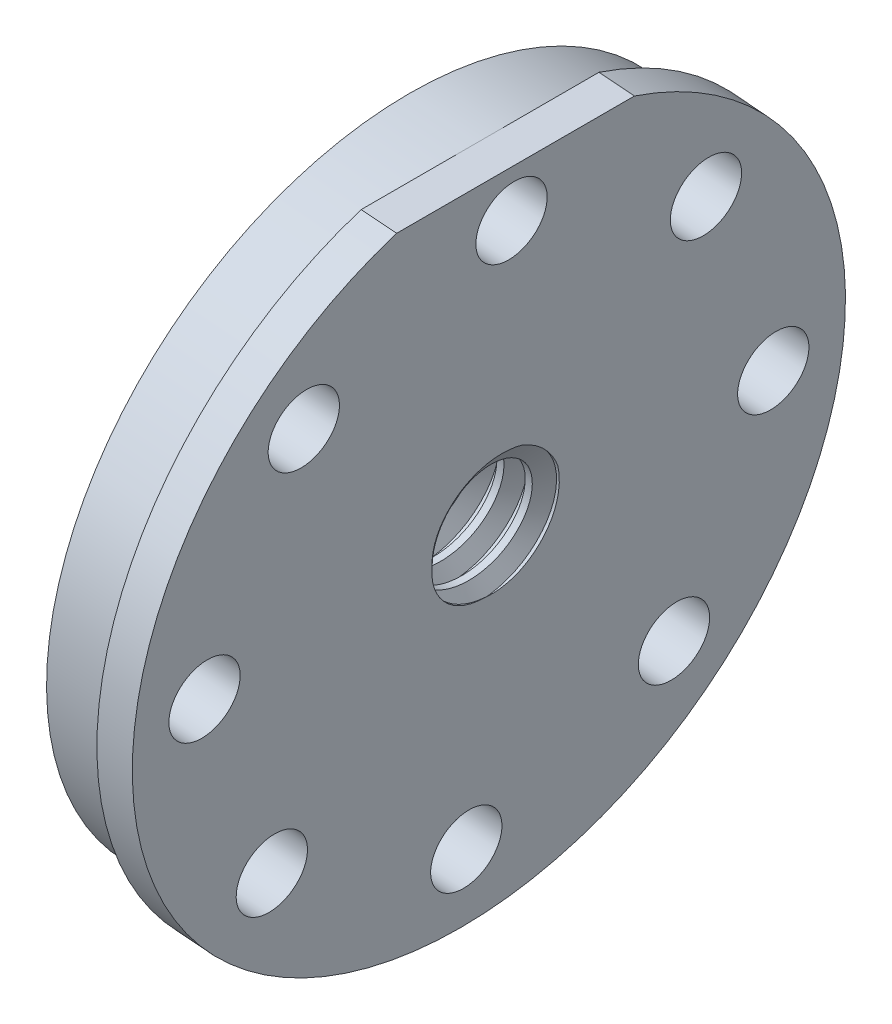
SolidWorks part; units mm, degrees
ref_plane "Front Plane" through (0, 0, 0) normal (0, 0, 1) x (1, 0, 0)
ref_plane "Top Plane" through (0, 0, 0) normal (0, 1, 0) x (1, 0, 0)
ref_plane "Right Plane" through (0, 0, 0) normal (1, 0, 0) x (0, 0, -1)
sketch "Sketch1" plane through (234.2789, -18.689, 0) normal (0.9968, -0.0795, 0) x (0, 0, -1)
  circle A1 centre (-43.1743, 8.5503) radius 14.9606
  dimension "D1" = 29.9212
extrude "Boss-Extrude1" add sketch "Sketch1" against normal blind 4.7625
sketch "Sketch2" plane through (234.2789, -18.689, 0) normal (0.9968, -0.0795, 0) x (0, 0, -1)
  circle A0 centre (-43.1743, 8.5503) radius 2.54
  dimension "D1" = 5.08
extrude "Cut-Extrude1" cut sketch "Sketch2" against normal blind 6.35
sketch "Sketch3" plane through (229.5315, -18.3103, 0) normal (-0.9968, 0.0795, 0) x (0, 0, 1)
  circle A0 centre (43.1743, 21.2503) radius 1.5875
  circle A1 centre (43.1743, 8.5503) radius 14.9606 construction
  circle A2 centre (43.1743, 8.5503) radius 14.9606
  circle A3 centre (52.1545, 17.5306) radius 1.5875
  circle A4 centre (55.8743, 8.5503) radius 1.5875
  circle A5 centre (52.1545, -0.4299) radius 1.5875
  circle A6 centre (43.1743, -4.1497) radius 1.5875
  circle A7 centre (34.194, -0.4299) radius 1.5875
  circle A8 centre (30.4743, 8.5503) radius 1.5875
  circle A9 centre (34.194, 17.5306) radius 1.5875
  point P21 (43.1743, 8.5503)
  dimension "D1" = 3.175
  dimension "D3" = 12.7
  dimension "D2" = 8
extrude "Cut-Extrude2" cut sketch "Sketch3" against normal blind 10 contours A8 | A0 | A3 | A4 | A5 | A6 | A7 | A9 region at (231.2213, 2.8727, 43.1743) region at (230.9255, -0.8352, 52.1545) region at (230.2114, -9.787, 55.8743) region at (229.4973, -18.7389, 52.1545) region at (229.2015, -22.4468, 43.1743) region at (229.4973, -18.7389, 34.194) region at (230.2114, -9.787, 30.4743)
sketch "Sketch4" plane through (234.2789, -18.689, 0) normal (0.9968, -0.0795, 0) x (0, 0, -1)
  line L0 (-58.1349, 8.5503) -> (-28.2137, 8.5503) construction
  circle A0 centre (-43.1743, 8.5503) radius 14.9606 construction
thread "Thread1" pitch 1.27 method cut profile "Thread Profile1" start angle 0, offset 0.9525, length 6.35, pitch 1.27, diameter 5.08
ref_plane "Plane1" through (235.9083, -10.2415, 45.7143) normal (-0.0795, -0.9968, 0) x (0, 0, 1)
sketch "Thread Profile1" plane through (235.9083, -10.2415, 45.7143) normal (-0.0795, -0.9968, 0) x (0, 0, 1)
  line L0 (0, 0) -> (0, 1.27) construction
  line L1 (0, 0) -> (0.6874, 0.3969)
  line L2 (0.6874, 0.3969) -> (0.6874, 0.5556)
  line L3 (0.6874, 0.5556) -> (0, 0.9525)
  line L4 (0.6874, 0.4762) -> (0, 0.4762) construction
  line L11 (0, 0) -> (0, 0.9525)
  point P2 (0, 0)
  dimension "Pitch" = 1.27
  dimension "Profile_Angle" = 60
  dimension "Profile_Land" = 0.1588
  dimension "Profile_Height" = 0.6874
sketch "Sketch5" plane through (234.2789, -18.689, 0) normal (-0.9968, 0.0795, 0) x (0, 0, 1)
  circle A0 centre (43.1743, 8.5503) radius 14.9606 construction
  circle A1 centre (43.1743, 8.5503) radius 14.9606
  circle A2 centre (43.1743, 8.5503) radius 15.875
  dimension "D1" = 31.75
extrude "Boss-Extrude2" add sketch "Sketch5" along normal blind 1.5875
ref_axis "Axis1" through (230.2455, -9.7898, 43.1743) along (0.9968, -0.0795, 0)
ref_point "Point1"
sketch "Sketch6" plane through (234.2789, -18.689, 0) normal (0.9968, -0.0795, 0) x (0, 0, -1)
  line L0 (-48.4843, 23.5109) -> (-37.8643, 23.5109)
  circle A0 centre (-43.1743, 8.5503) radius 15.875 construction
  circle A1 centre (-43.1743, 8.5503) radius 14.9606 construction
  circle A2 centre (-43.1743, 8.5503) radius 15.875
  circle A3 centre (-43.1743, 8.5503) radius 15.875
  circle M15 centre (-43.1743, 8.5503) radius 15.875
  dimension "D1" = 0
extrude "Cut-Extrude3" cut sketch "Sketch6" against normal blind 2.54 contours L0 M15 region at (236.1776, 5.113, 43.1743)
